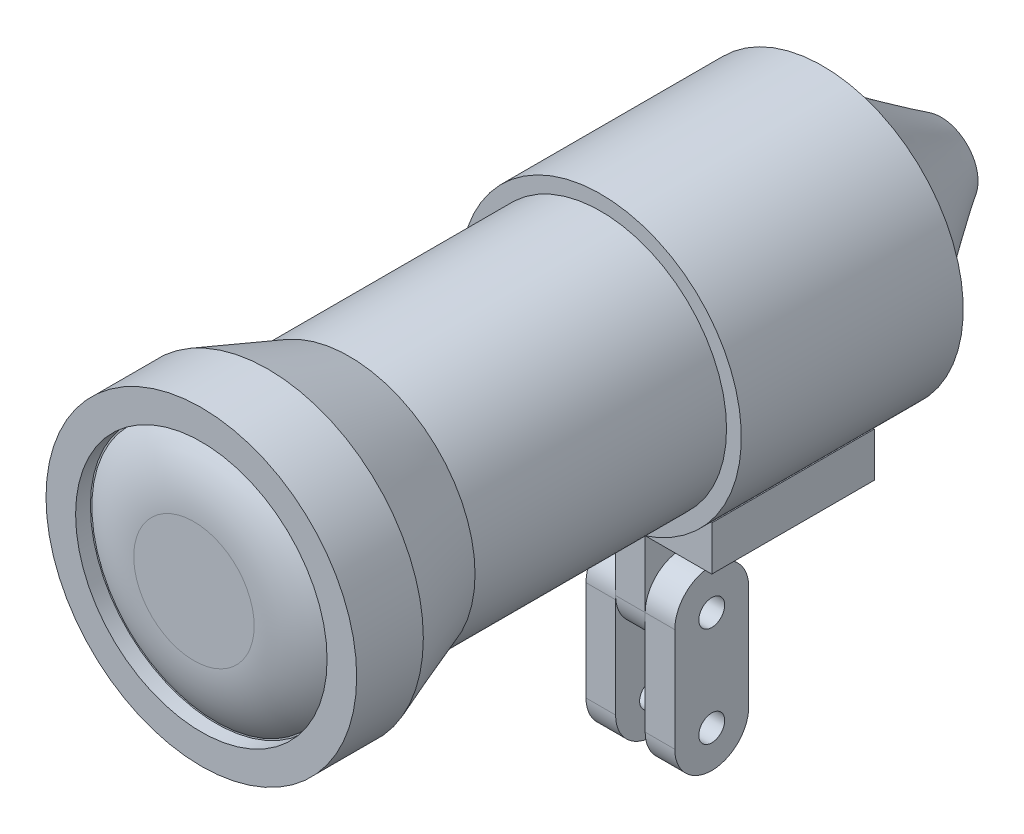
SolidWorks part; units mm, degrees
ref_plane "Front Plane" through (0, 0, 0) normal (0, 0, 1) x (1, 0, 0)
ref_plane "Top Plane" through (0, 0, 0) normal (0, 1, 0) x (1, 0, 0)
ref_plane "Right Plane" through (0, 0, 0) normal (1, 0, 0) x (0, 0, -1)
sketch "Sketch1" plane through (0, 0, 0) normal (0, 0, 1) x (1, 0, 0)
  circle A0 centre (0, 0) radius 8.5
  dimension "D1" = 17
extrude "Boss-Extrude1" add sketch "Sketch1" against normal blind 17 contours A0
sketch "Sketch2" plane through (0, 0, 0) normal (0, 0, 1) x (1, 0, 0)
  circle A0 centre (0, 0) radius 10.5
  dimension "D1" = 21
extrude "Boss-Extrude2" add sketch "Sketch2" along normal blind 10
chamfer "Chamfer1" distance 2 angle 70 1 edges at (10.5, 0, 0) first distance on face at (8.5, 0, 0)
sketch "Sketch3" plane through (0, 0, 10) normal (0, 0, 1) x (1, 0, 0)
  circle A0 centre (0, 0) radius 8.5
  dimension "D1" = 17
extrude "Cut-Extrude1" cut sketch "Sketch3" against normal blind 1
sketch "Sketch4" plane through (0, 0, -17) normal (0, 0, -1) x (-1, 0, 0)
  circle A0 centre (0, 0) radius 9.5
  dimension "D1" = 19
extrude "Boss-Extrude3" add sketch "Sketch4" along normal blind 15
ref_plane "Plane1" through (0, 0, -40) normal (0, 0, -1) x (-1, 0, 0)
sketch "Sketch6" plane through (0, 0, -40) normal (0, 0, -1) x (-1, 0, 0)
  circle A0 centre (0, 0) radius 2.5
  dimension "D1" = 5
sketch "Sketch7" plane through (0, 0, -32) normal (0, 0, -1) x (-1, 0, 0)
  circle A0 centre (0, 0) radius 8
  dimension "D1" = 16
loft "Loft2" add profiles "Sketch7", "Sketch6" connector at (5.6817, 5.6319, -32) connector at (2.2759, 1.0345, -40)
ref_plane "Plane2" through (0, -8, 0) normal (0, 1, 0) x (1, 0, 0)
sketch "Sketch9" plane through (0, -8, 0) normal (0, 1, 0) x (1, 0, 0)
  line L1 (-5.5, 19) -> (5.5, 19)
  line L2 (-5.5, 19) -> (-5.5, 30)
  line L3 (-5.5, 30) -> (5.5, 30)
  line L4 (5.5, 19) -> (5.5, 30)
  line L5 (9.5, 17) -> (9.5, 32) construction
  line L6 (-9.5, 32) -> (-9.5, 17) construction
  line L7 (8, 32) -> (-8, 32) construction
  line L8 (-9.5, 17) -> (9.5, 17) construction
  dimension "D1" = 4
  dimension "D2" = 4
  dimension "D3" = 2
  dimension "D4" = 2
extrude "Boss-Extrude4" add sketch "Sketch9" against normal blind 3 contours L2 L3 L4 L1
sketch "Sketch10" plane through (0, -11, 0) normal (0, -1, 0) x (1, 0, 0)
  line L0 (-5.5, -19) -> (5.5, -19) construction
  line L5 (1, -19) -> (-1, -19)
  line L6 (1, -19) -> (1, -24)
  line L7 (1, -24) -> (-1, -24)
  line L8 (-1, -19) -> (-1, -24)
  line L9 (5.5, -19) -> (5.5, -30) construction
  dimension "D1" = 2
  dimension "D2" = 5
  dimension "D3" = 4.5
extrude "Boss-Extrude5" add sketch "Sketch10" along normal blind 7
fillet "Fillet1" radius 2.5 2 edges at (0, -18, -19) (0, -18, -24)
sketch "Sketch13" plane through (0, 0, 9) normal (0, 0, 1) x (1, 0, 0)
  circle A0 centre (0, 0) radius 8.4
  dimension "D1" = 16.8
extrude "Boss-Extrude7" add sketch "Sketch13" along normal blind 1.5
fillet "Fillet3" radius 7 1 edges at (8.4, 0, 10.5)
sketch "Sketch14" plane through (1, 0, 0) normal (1, 0, 0) x (0, 0, -1)
  line L0 (24, -15.5) -> (24, -11) construction
  line L1 (19, -13) -> (24, -13)
  line L2 (19, -13) -> (19, -25)
  line L3 (19, -25) -> (24, -25)
  line L4 (24, -13) -> (24, -25)
  line L5 (19, -15.5) -> (19, -11) construction
  dimension "D1" = 12
  dimension "D2" = 5
extrude "Boss-Extrude9" add sketch "Sketch14" along normal blind 2 contours L2 L3 L4 L1
sketch "Sketch15" plane through (-1, 0, 0) normal (-1, 0, 0) x (0, 0, 1)
  line L0 (-24, -25) -> (-24, -13.25)
  line L1 (-24, -15.5) -> (-24, -11) construction
  line L2 (-24, -13.25) -> (-19, -13.25)
  line L3 (-19, -15.5) -> (-19, -11) construction
  line L4 (-19, -13.25) -> (-19, -25)
  line L5 (-19, -25) -> (-24, -25)
extrude "Boss-Extrude10" add sketch "Sketch15" along normal blind 2
fillet "Fillet4" radius 2.5 8 edges at (2, -25, -19) (-2, -25, -19) (2, -25, -24) (-2, -25, -24) (2, -13, -24) (-2, -13.25, -24) (2, -13, -19) (-2, -13.25, -19)
sketch "Sketch16" plane through (-3, 0, 0) normal (-1, 0, 0) x (0, 0, 1)
  circle A0 centre (-21.5, -15.75) radius 0.875
  circle A1 centre (-21.5, -22.5) radius 0.875
  dimension "D1" = 1.75
  dimension "D2" = 1.75
extrude "Cut-Extrude3" cut sketch "Sketch16" against normal up to surface (6 mm away) up to face at (3, -19, -21.5)
